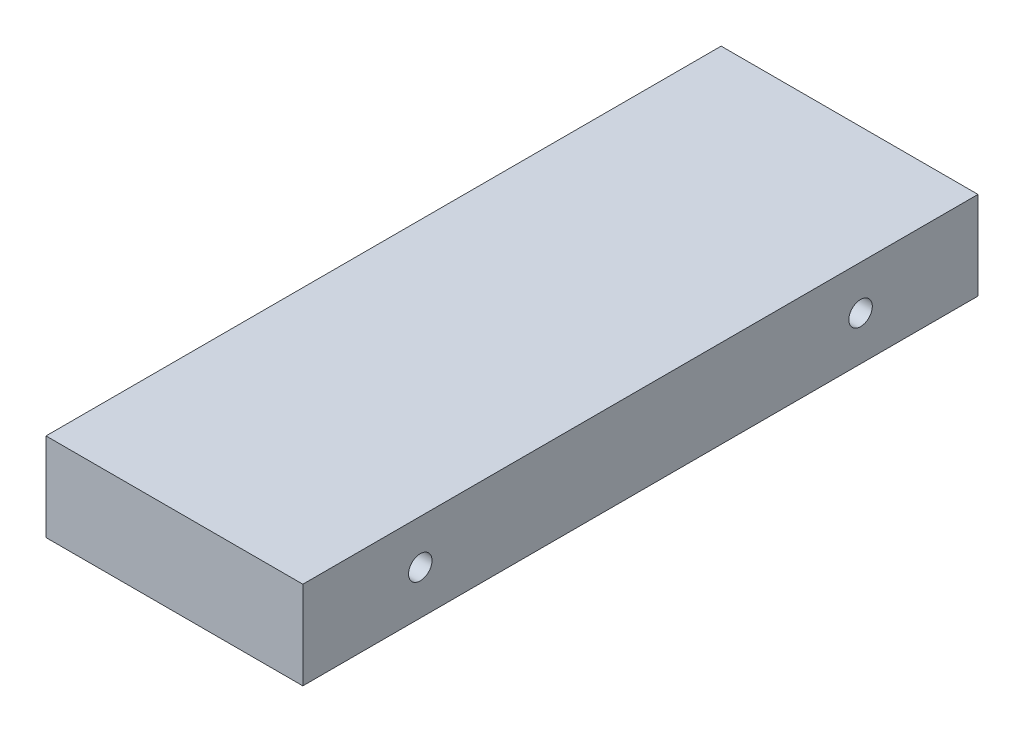
SolidWorks part; units mm, degrees
ref_plane "Front Plane" through (0, 0, 0) normal (0, 0, 1) x (1, 0, 0)
ref_plane "Top Plane" through (0, 0, 0) normal (0, 1, 0) x (1, 0, 0)
ref_plane "Right Plane" through (0, 0, 0) normal (1, 0, 0) x (0, 0, -1)
sketch "Sketch1" plane through (0, 0, 0) normal (1, 0, 0) x (0, 0, -1)
  line L1 (-46, 6) -> (46, 6)
  line L2 (-46, 6) -> (-46, -6)
  line L3 (-46, -6) -> (46, -6)
  line L4 (46, 6) -> (46, -6)
  line L5 (-46, 6) -> (46, -6) construction
  line L6 (-46, -6) -> (46, 6) construction
  circle A0 centre (-30, 0) radius 4
  circle A1 centre (-30, 0) radius 1.6
  circle A2 centre (30, 0) radius 4
  circle A3 centre (30, 0) radius 1.6
  circle A4 centre (-42, 0) radius 1.621
  circle A5 centre (42, 0) radius 1.621
  point P0 (0, 0)
  dimension "D5" = 3.2
  dimension "D6" = 8
  dimension "D7" = 3.242
  dimension "D8" = 84
  dimension "D9" = 42
  dimension "D1" = 12
  dimension "D2" = 92
  dimension "D3" = 30
  dimension "D4" = 30
extrude "Boss-Extrude1" add sketch "Sketch1" along normal blind 35 contours L2 L3 L4 L1
extrude "Cut-Extrude1" cut sketch "Sketch1<4>" along normal blind 27 contours A0 | A2
sketch "Sketch1<4>" plane through (0, 0, 0) normal (1, 0, 0) x (0, 0, -1) same geometry as "Sketch1"
extrude "Cut-Extrude2" cut sketch "Sketch1<5>" along normal blind 35 contours A3 | A1
sketch "Sketch1<5>" plane through (0, 0, 0) normal (1, 0, 0) x (0, 0, -1) same geometry as "Sketch1"
extrude "Cut-Extrude3" cut sketch "Sketch1<6>" along normal blind 12 contours A5 | A4
sketch "Sketch1<6>" plane through (0, 0, 0) normal (1, 0, 0) x (0, 0, -1) same geometry as "Sketch1"
